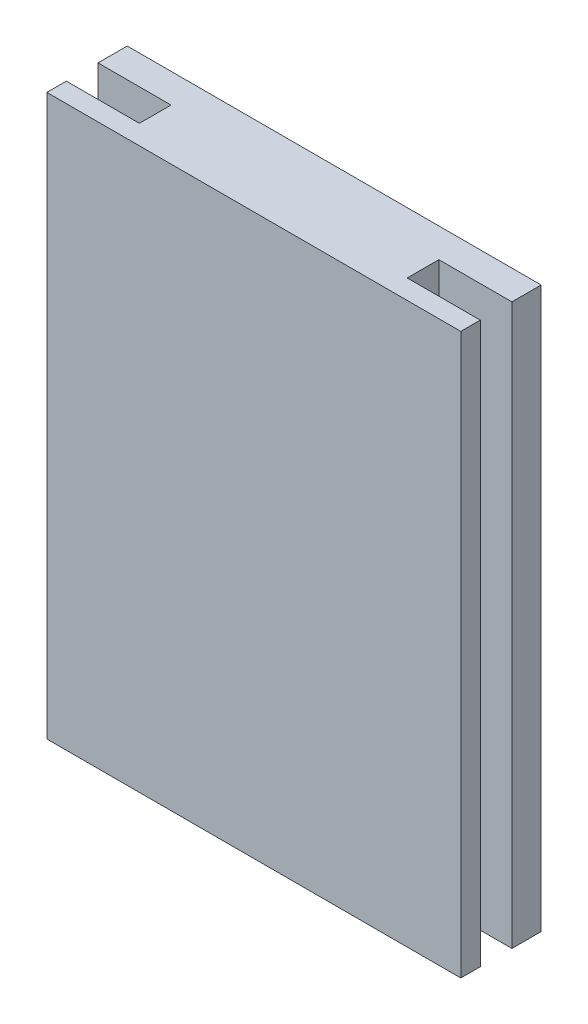
SolidWorks part; units mm, degrees
material "1060 Alloy"
ref_plane "Front" through (0, 0, 0) normal (0, 0, 1) x (1, 0, 0)
ref_plane "Top" through (0, 0, 0) normal (0, 1, 0) x (1, 0, 0)
ref_plane "Right" through (0, 0, 0) normal (1, 0, 0) x (0, 0, -1)
sketch "Sketch2" plane through (0, 0, 0) normal (0, 0, 1) x (1, 0, 0)
  line L1 (0, 0) -> (85, 0)
  line L2 (0, 0) -> (0, 115)
  line L3 (0, 115) -> (85, 115)
  line L4 (85, 0) -> (85, 115)
  dimension "D1" = 85
  dimension "D2" = 115
extrude "Boss-Extrude1" add sketch "Sketch2" along normal blind 15
sketch "Sketch3" plane through (0, 115, 0) normal (0, 1, 0) x (1, 0, 0)
  line L1 (0, -15) -> (15, -15)
  line L2 (0, -15) -> (0, -10.5)
  line L3 (0, -10.5) -> (15, -10.5)
  line L4 (15, -15) -> (15, -10.5)
  dimension "D1" = 15
  dimension "D2" = 4.5
ref_plane "Plane1" through (0, 0, 7.5) normal (0, 0, 1) x (1, 0, 0)
ref_plane "Plane2" through (42.5, 0, 0) normal (-1, 0, 0) x (0, 0, 1)
ref_axis "Axis1" through (42.5, 120.75, 7.5) along (0, -1, 0)
extrude "Cut-Extrude1" cut sketch "Sketch3" against normal through all
mirror "Mirror1" about plane through (0, 0, 7.5) normal (0, 0, 1) of "Cut-Extrude1"
mirror "Mirror2" about plane through (42.5, 0, 0) normal (-1, 0, 0) of "Mirror1"
sketch "Sketch4" plane through (0, 0, 15) normal (0, 0, 1) x (1, 0, 0)
  line L1 (15, 115) -> (70, 115)
  line L2 (15, 115) -> (15, 0)
  line L3 (15, 0) -> (70, 0)
  line L4 (70, 115) -> (70, 0)
extrude "Boss-Extrude2" add sketch "Sketch4" along normal blind 2
sketch "Sketch6" plane through (0, 0, 0) normal (0, 0, -1) x (-1, 0, 0)
  line L1 (-70, 115) -> (-15, 115)
  line L2 (-70, 115) -> (-70, 0)
  line L3 (-70, 0) -> (-15, 0)
  line L4 (-15, 115) -> (-15, 0)
extrude "Cut-Extrude2" cut sketch "Sketch6" against normal up to surface (4.5 mm away) up to face at (77.5, 57.5, 4.5)
sketch "Sketch5" plane through (0, 0, 17) normal (0, 0, 1) x (1, 0, 0)
  line L1 (0, 115) -> (85, 115)
  line L2 (0, 115) -> (0, 0)
  line L3 (0, 0) -> (85, 0)
  line L4 (85, 115) -> (85, 0)
extrude "Boss-Extrude3" add sketch "Sketch5" along normal blind 4
